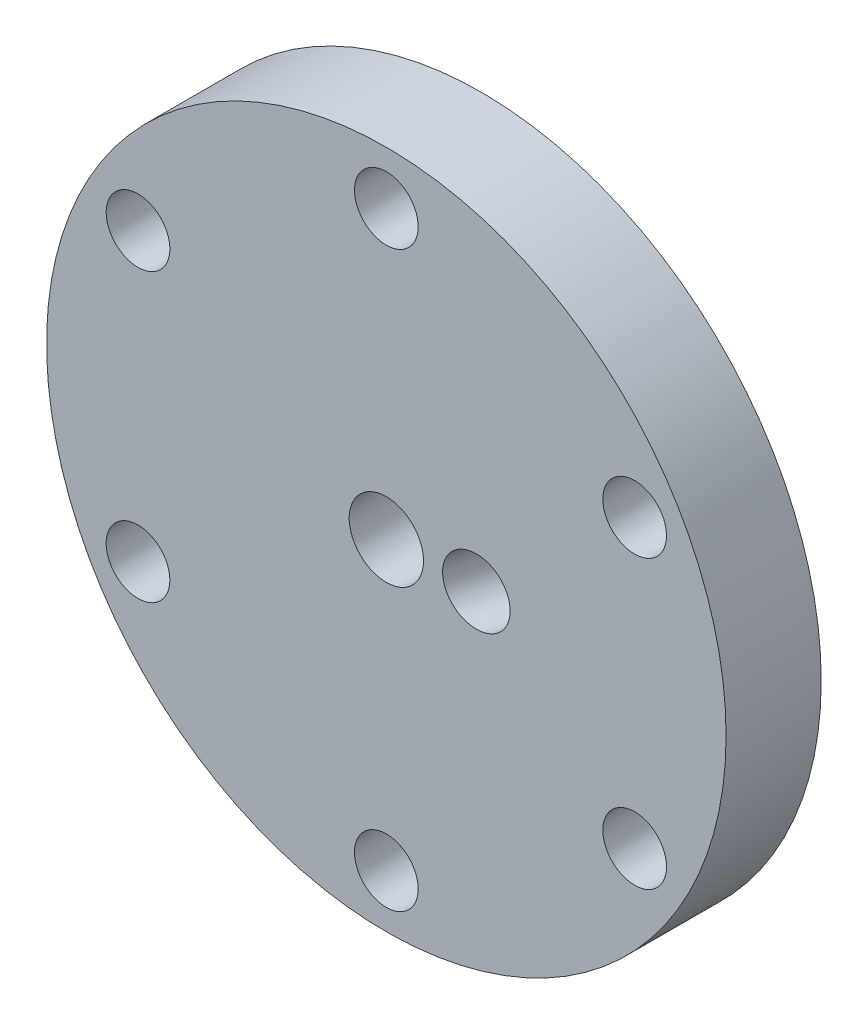
SolidWorks part; units mm, degrees
ref_plane "Front Plane" through (0, 0, 0) normal (0, 0, 1) x (1, 0, 0)
ref_plane "Top Plane" through (0, 0, 0) normal (0, 1, 0) x (1, 0, 0)
ref_plane "Right Plane" through (0, 0, 0) normal (1, 0, 0) x (0, 0, -1)
ref_axis "Axis1" through (0, 0, -88.99) along (0, 0, 1)
sketch "Sketch1" plane through (0, 0, 0) normal (0, 0, 1) x (1, 0, 0)
  circle A0 centre (0, 0) radius 50.8
extrude "Boss-Extrude1" add sketch "Sketch1" along normal mid plane 14.224
sketch "Sketch2" plane through (0, 0, 7.112) normal (0, 0, 1) x (1, 0, 0)
  circle A0 centre (0, 0) radius 5.5562
extrude "Cut-Extrude1" cut sketch "Sketch2" against normal through all
sketch "Sketch3" plane through (0, 0, 7.112) normal (0, 0, 1) x (1, 0, 0)
  circle A0 centre (0, 42.8752) radius 4.7625
  dimension "D1" = 9.525
  dimension "D2" = 42.8752
extrude "Cut-Extrude2" cut sketch "Sketch3" against normal through all
pattern_circular "CirPattern1" count 6 over 360 about axis through (0, 0, -88.99) along (0, 0, 1) of "Cut-Extrude2" reverse direction yes
ref_plane "Plane1" through (13.462, 0, 0) normal (1, 0, 0) x (0, 0, -1)
ref_axis "Axis2" through (13.462, 55.88, 7.112) along (0, -1, 0)
ref_plane "Plane2" through (-0.8762, 0, 3.2701) normal (-0.2588, 0, 0.9659) x (0, -1, 0)
sketch "Sketch5" plane through (-0.8762, 0, 3.2701) normal (-0.2588, 0, 0.9659) x (0, -1, 0)
  line L0 (-55.88, 14.844) -> (55.88, 14.844) construction
  circle A0 centre (0, 14.844) radius 4.8768
  dimension "D2" = 9.7536
  dimension "D1" = 0
extrude "Cut-Extrude3" cut sketch "Sketch5" against normal mid plane 50.8 contours A0
